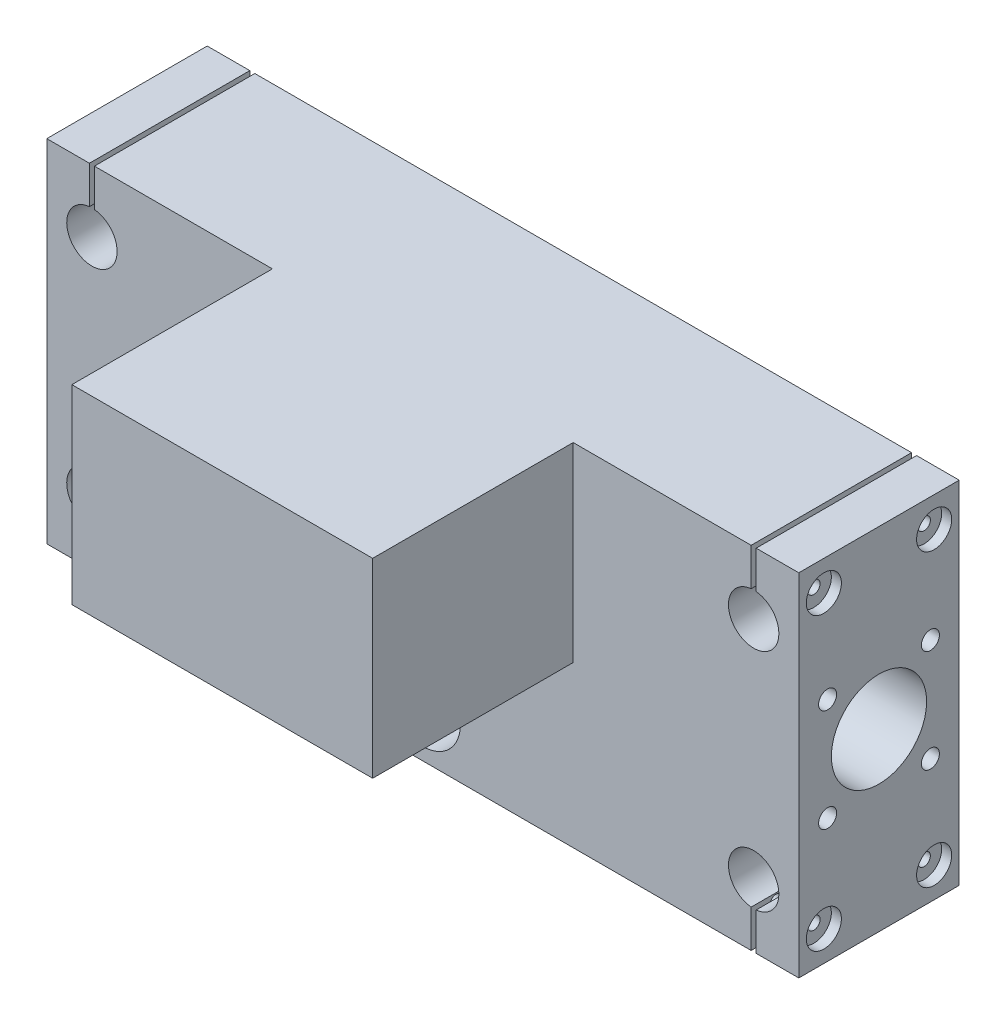
SolidWorks part; units mm, degrees
material "1060 Alloy"
ref_plane "Front Plane" through (0, 0, 0) normal (0, 0, 1) x (1, 0, 0)
ref_plane "Top Plane" through (0, 0, 0) normal (0, 1, 0) x (1, 0, 0)
ref_plane "Right Plane" through (0, 0, 0) normal (1, 0, 0) x (0, 0, -1)
sketch "Sketch1" plane through (0, 0, 0) normal (0, 0, 1) x (1, 0, 0)
  line L1 (-150, 0) -> (0, 0)
  line L2 (-150, 0) -> (-150, -70)
  line L3 (-150, -70) -> (0, -70)
  line L4 (0, 0) -> (0, -70)
  dimension "D1" = 150
  dimension "D2" = 70
extrude "Boss-Extrude1" add sketch "Sketch1" along normal blind 32
sketch "Sketch2" plane through (-150, 0, 0) normal (-1, 0, 0) x (0, 0, 1)
  line L0 (16, 0) -> (16, -70) construction
  line L1 (32, 0) -> (0, 0) construction
  line L2 (32, -70) -> (0, -70) construction
  line L3 (0, -35) -> (32, -35) construction
  line L4 (0, 0) -> (0, -70) construction
  line L5 (32, 0) -> (32, -70) construction
  circle A0 centre (16, -35) radius 9.5
  dimension "D1" = 19
extrude "Linear_bearing-cut-1" cut sketch "Sketch2" against normal blind 55
sketch "Sketch5" plane through (0, 0, 32) normal (0, 0, 1) x (1, 0, 0)
  line L0 (-75, 0) -> (-75, -70) construction
  line L1 (0, 0) -> (-150, 0) construction
  line L2 (-150, -70) -> (0, -70) construction
  line L3 (0, -35) -> (-150, -35) construction
  line L4 (0, -70) -> (0, 0) construction
  line L5 (-150, 0) -> (-150, -70) construction
  line L6 (-141, 0) -> (-141, -12.5) construction
  line L7 (-141, -12.5) -> (-9, -12.5) construction
  line L8 (-9, -12.5) -> (-9, 0) construction
  line L9 (-9, -57.5) -> (-9, -70) construction
  line L10 (-141, -57.5) -> (-9, -57.5) construction
  line L11 (-141, -70) -> (-141, -57.5) construction
  line L12 (-141.5, 0) -> (-141.5, -7.5)
  line L13 (-140.5, 0) -> (-140.5, -7.5)
  line L14 (-8.5, 0) -> (-8.5, -7.5)
  line L15 (-9.5, 0) -> (-9.5, -7.5)
  line L16 (-141.5, -70) -> (-141.5, -62.5)
  line L17 (-140.5, -70) -> (-140.5, -62.5)
  line L18 (-9.5, -70) -> (-9.5, -62.5)
  line L19 (-8.5, -70) -> (-8.5, -62.5)
  line L20 (-141.5, 0) -> (-140.5, 0)
  line L21 (-9.5, 0) -> (-8.5, 0)
  line L22 (-9.5, -70) -> (-8.5, -70)
  line L23 (-141.5, -70) -> (-140.5, -70)
  arc A0 (-141.5, -7.5) -> (-140.5, -7.5) centre (-141, -12.5) ccw
  arc A1 (-8.5, -7.5) -> (-9.5, -7.5) centre (-9, -12.5) cw
  arc A2 (-141.5, -62.5) -> (-140.5, -62.5) centre (-141, -57.5) cw
  arc A3 (-8.5, -62.5) -> (-9.5, -62.5) centre (-9, -57.5) ccw
  dimension "D1" = 9
  dimension "D3" = 12.5
  dimension "D5" = 0.5
  dimension "D6" = 7.5
extrude "Y-axis-shafts-cut" cut sketch "Sketch5" against normal through all
sketch "Sketch6" plane through (-95, 0, 0) normal (-1, 0, 0) x (0, 0, 1)
  line L0 (16, -25.5) -> (16, -44.5) construction
  circle A0 centre (16, -35) radius 9.5 construction
  circle A1 centre (16, -35) radius 9.5 construction
  circle A2 centre (16, -35) radius 6
  dimension "D1" = 12
sketch "Sketch7" plane through (0, 0, 0) normal (1, 0, 0) x (0, 0, -1)
  circle A0 centre (-16, -35) radius 9.5
  dimension "D1" = 19
extrude "Linear-bearing-cut-2" cut sketch "Sketch7" against normal blind 55
extrude "between-bearings" cut sketch "Sketch6" against normal through all
sketch "Sketch8" plane through (-150, 0, 0) normal (-1, 0, 0) x (0, 0, 1)
  line L0 (5, 0) -> (5, -6) construction
  line L1 (32, 0) -> (0, 0) construction
  line L2 (5, -6) -> (27, -6) construction
  line L3 (27, -6) -> (27, 0) construction
  line L4 (0, 0) -> (0, -70) construction
  line L5 (32, 0) -> (32, -70) construction
  line L6 (16, 0) -> (16, -70) construction
  line L7 (32, -70) -> (0, -70) construction
  line L8 (0, -35) -> (32, -35) construction
  line L9 (5, -39.9148) -> (4.7174, -39.9148) construction
  circle A0 centre (5, -6) radius 3.5
  circle A1 centre (27, -6) radius 3.5
  circle A2 centre (27, -64) radius 3.5
  circle A3 centre (5, -64) radius 3.5
  dimension "D4" = 7
  dimension "D1" = 5
  dimension "D3" = 6
extrude "shaft-holder-screw-cut" cut sketch "Sketch8" against normal blind 4
sketch "Sketch9" plane through (-146, 0, 0) normal (-1, 0, 0) x (0, 0, 1)
  line L0 (5, -2.5) -> (5, -9.5) construction
  line L1 (27, -2.5) -> (27, -9.5) construction
  line L2 (27, -60.5) -> (27, -67.5) construction
  line L3 (5, -60.5) -> (5, -67.5) construction
  circle A0 centre (5, -6) radius 3.5 construction
  circle A1 centre (5, -6) radius 3.5 construction
  circle A2 centre (27, -6) radius 3.5 construction
  circle A3 centre (27, -6) radius 3.5 construction
  circle A4 centre (27, -64) radius 3.5 construction
  circle A5 centre (27, -64) radius 3.5 construction
  circle A6 centre (5, -64) radius 3.5 construction
  circle A7 centre (5, -64) radius 3.5 construction
  circle A8 centre (5, -6) radius 1.25
  circle A9 centre (27, -6) radius 1.25
  circle A10 centre (5, -64) radius 1.25
  circle A11 centre (27, -64) radius 1.25
  dimension "D1" = 2.5
extrude "shaft-holder-screw-cut2" cut sketch "Sketch9" against normal blind 20
sketch "Sketch10" plane through (0, 0, 0) normal (1, 0, 0) x (0, 0, -1)
  line L0 (-27, 0) -> (-27, -6) construction
  line L1 (-32, 0) -> (0, 0) construction
  line L2 (-27, -6) -> (-5, -6) construction
  line L3 (-5, -6) -> (-5, 0) construction
  line L4 (-32, -70) -> (-32, 0) construction
  line L5 (0, -70) -> (0, 0) construction
  line L6 (-16, 0) -> (-16, -70) construction
  line L7 (-32, -70) -> (0, -70) construction
  line L8 (-32, -35) -> (0, -35) construction
  circle A0 centre (-27, -6) radius 3.5
  circle A1 centre (-5, -6) radius 3.5
  circle A2 centre (-5, -64) radius 3.5
  circle A3 centre (-27, -64) radius 3.5
  dimension "D4" = 7
  dimension "D1" = 5
  dimension "D2" = 6
extrude "shaft-holder-screw-cut-3" cut sketch "Sketch10" against normal blind 2
sketch "Sketch11" plane through (-2, 0, 0) normal (1, 0, 0) x (0, 0, -1)
  line L0 (-27, -2.5) -> (-27, -9.5) construction
  line L1 (-5, -2.5) -> (-5, -9.5) construction
  line L2 (-5, -60.5) -> (-5, -67.5) construction
  line L3 (-27, -60.5) -> (-27, -67.5) construction
  circle A0 centre (-27, -6) radius 3.5 construction
  circle A1 centre (-27, -6) radius 3.5 construction
  circle A2 centre (-5, -6) radius 3.5 construction
  circle A3 centre (-5, -6) radius 3.5 construction
  circle A4 centre (-5, -64) radius 3.5 construction
  circle A5 centre (-5, -64) radius 3.5 construction
  circle A6 centre (-27, -64) radius 3.5 construction
  circle A7 centre (-27, -64) radius 3.5 construction
  circle A8 centre (-27, -6) radius 1.25
  circle A9 centre (-5, -6) radius 1.25
  circle A10 centre (-5, -64) radius 1.25
  circle A11 centre (-27, -64) radius 1.25
  dimension "D1" = 2.5
extrude "shaft-holder-screw-cut-4" cut sketch "Sketch11" against normal blind 20
sketch "Sketch12" plane through (0, 0, 0) normal (1, 0, 0) x (0, 0, -1)
  line L0 (-5.75, 0) -> (-5.75, -24.75) construction
  line L1 (-32, 0) -> (0, 0) construction
  line L2 (-5.75, -24.75) -> (0, -24.75) construction
  line L3 (0, -70) -> (0, 0) construction
  line L4 (-16, 0) -> (-16, -70) construction
  line L5 (-32, -70) -> (0, -70) construction
  line L6 (0, -35) -> (-32, -35) construction
  line L7 (-32, -70) -> (-32, 0) construction
  circle A0 centre (-5.75, -24.75) radius 1.8
  circle A1 centre (-26.25, -24.75) radius 1.8
  circle A2 centre (-5.75, -45.25) radius 1.8
  circle A3 centre (-26.25, -45.25) radius 1.8
  dimension "D3" = 3.6
  dimension "D1" = 5.75
  dimension "D2" = 24.75
extrude "Linear-bearing-srew1" cut sketch "Sketch12" against normal blind 14
sketch "Sketch13" plane through (-150, 0, 0) normal (-1, 0, 0) x (0, 0, 1)
  line L0 (27.5, 0) -> (27.5, -24.75) construction
  line L1 (32, 0) -> (0, 0) construction
  line L2 (27.5, -24.75) -> (32, -24.75) construction
  line L3 (32, 0) -> (32, -70) construction
  line L4 (16, 0) -> (16, -70) construction
  line L5 (32, -70) -> (0, -70) construction
  line L6 (32, -35) -> (0, -35) construction
  line L7 (0, 0) -> (0, -70) construction
  circle A0 centre (27.5, -24.75) radius 1.85
  circle A1 centre (4.5, -24.75) radius 1.85
  circle A2 centre (27.5, -45.25) radius 1.85
  circle A3 centre (4.5, -45.25) radius 1.85
  dimension "D3" = 3.7
  dimension "D1" = 24.75
  dimension "D2" = 4.5
extrude "Linear-bearing-screw2" cut sketch "Sketch13" against normal blind 14
sketch "Sketch14" plane through (0, 0, 32) normal (0, 0, 1) x (1, 0, 0)
  line L1 (0, -70) -> (0, 0) construction
  line L2 (-140.5, -70) -> (-9.5, -70) construction
  circle A0 centre (-75, -60) radius 7.5
  point P2 (0, 0)
  dimension "D1" = 15
  dimension "D2" = 75
  dimension "D3" = 10
extrude "Cut-Extrude1" cut sketch "Sketch14" against normal through all
sketch "Sketch16" plane through (0, 0, 32) normal (0, 0, 1) x (1, 0, 0)
  line L0 (-9.5, 0) -> (-140.5, 0) construction
  line L1 (-105, 0) -> (-45, 0)
  line L2 (-105, 0) -> (-105, -38)
  line L3 (-105, -38) -> (-45, -38)
  line L4 (-45, 0) -> (-45, -38)
  line L5 (-75, -70) -> (-75, 0) construction
  line L6 (-140.5, -70) -> (-9.5, -70) construction
  point P10 (-75, 0)
  dimension "D1" = 38
  dimension "D2" = 60
extrude "Boss-Extrude3" add sketch "Sketch16" along normal blind 40
